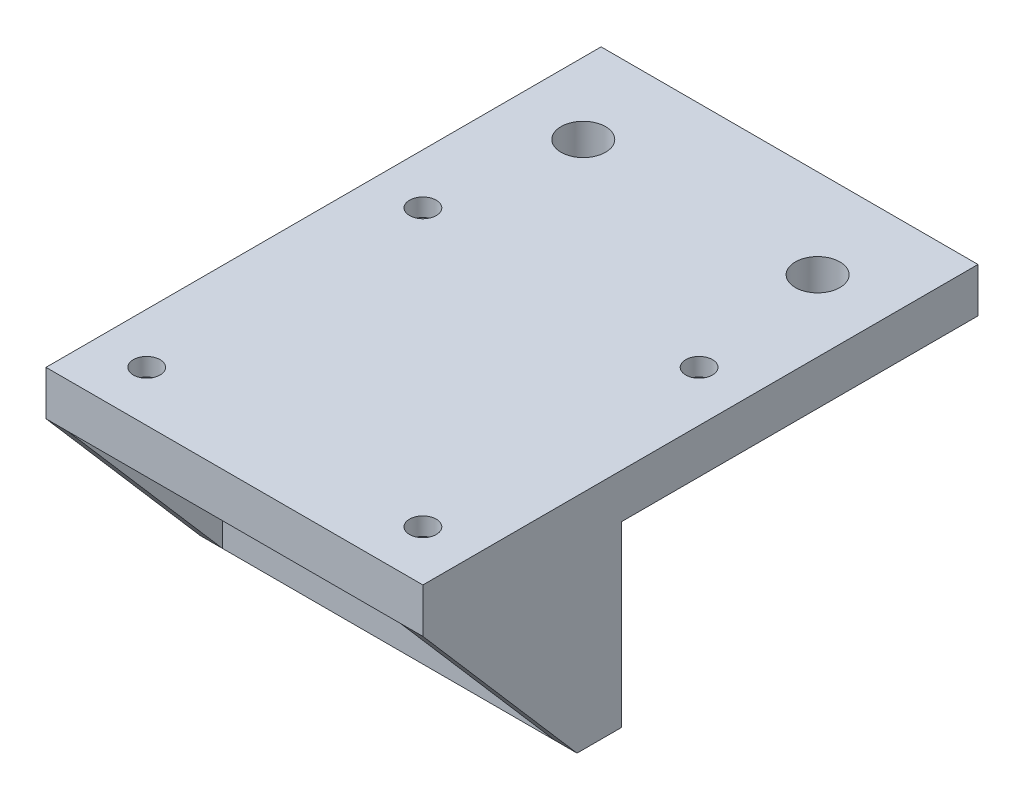
SolidWorks part; units mm, degrees
material "PET"
ref_plane "Front Plane" through (0, 0, 0) normal (0, 0, 1) x (1, 0, 0)
ref_plane "Top Plane" through (0, 0, 0) normal (0, 1, 0) x (1, 0, 0)
ref_plane "Right Plane" through (0, 0, 0) normal (1, 0, 0) x (0, 0, -1)
sketch "Sketch1" plane through (0, 0, 0) normal (0, 1, 0) x (1, 0, 0)
  line L0 (21.15, 21.15) -> (-21.15, -21.15) construction
  line L1 (-21.15, -21.15) -> (21.15, -21.15)
  line L2 (-21.15, -21.15) -> (-21.15, 21.15)
  line L4 (21.15, -21.15) -> (21.15, 21.15)
  line L5 (-15.5, 15.5) -> (15.5, -15.5) construction
  line L8 (-21.15, 21.15) -> (-21.15, 41.15)
  line L9 (-21.15, 41.15) -> (21.15, 41.15)
  line L10 (21.15, 21.15) -> (21.15, 41.15)
  circle A0 centre (-15.5, 15.5) radius 1.5
  circle A1 centre (15.5, 15.5) radius 1.5
  circle A2 centre (-15.5, -15.5) radius 1.5
  circle A3 centre (15.5, -15.5) radius 1.5
  point P4 (0, 0)
  point P15 (0, 0)
  point P17 (0, 0)
  dimension "D3" = 3
  dimension "D4" = 3
  dimension "D5" = 3
  dimension "D7" = 3
  dimension "D1" = 20
  dimension "D2" = 42.3
  dimension "D6" = 31
  dimension "D8" = 31
extrude "Boss-Extrude1" add sketch "Sketch1" along normal blind 5
sketch "Sketch2" plane through (0, 0, 0) normal (0, -1, 0) x (1, 0, 0)
  circle A0 centre (-15.5, 15.5) radius 2.75
  circle A1 centre (-15.5, -15.5) radius 2.75
  circle A2 centre (15.5, 15.5) radius 2.75
  circle A3 centre (15.5, -15.5) radius 2.75
  dimension "D1" = 5.5
  dimension "D2" = 5.5
  dimension "D3" = 5.5
  dimension "D4" = 5.5
extrude "Cut-Extrude1" cut sketch "Sketch2" against normal blind 3
sketch "Sketch3" plane through (0, 0, 0) normal (0, -1, 0) x (1, 0, 0)
  line L0 (21.15, 21.15) -> (21.15, -41.15) construction
  line L1 (-21.15, -21.15) -> (21.15, -21.15)
  line L2 (-21.15, -21.15) -> (-21.15, -1.15)
  line L3 (-21.15, -1.15) -> (21.15, -1.15)
  line L4 (21.15, -21.15) -> (21.15, -1.15)
  line L5 (21.15, -41.15) -> (-21.15, -41.15) construction
  line L6 (21.15, -1.15) -> (-21.15, -1.15)
  line L7 (21.15, -1.15) -> (21.15, 3.85)
  line L8 (21.15, 3.85) -> (-21.15, 3.85)
  line L9 (-21.15, -1.15) -> (-21.15, 3.85)
  line L10 (-21.15, -41.15) -> (-21.15, 21.15) construction
  line M8 (-21.15, 21.15) -> (-21.15, -41.15)
  line M10 (21.15, -41.15) -> (21.15, 21.15)
  dimension "D1" = 5
  dimension "D2" = 20
  dimension "D3" = 20
extrude "Boss-Extrude2" add sketch "Sketch3" along normal blind 20 contours L8 L3 M10 M8 region at (0, 0, 1.35)
sketch "Sketch7" plane through (0, 1.15, 3.85) normal (0, 0, -1) x (1, 0, 0)
  line L1 (-21.15, 21.15) -> (21.15, 21.15) construction
  line L2 (-21.15, 21.15) -> (-21.15, 1.15) construction
  line L3 (-21.15, 1.15) -> (21.15, 1.15) construction
  line L4 (21.15, 21.15) -> (21.15, 1.15) construction
  line L5 (-21.15, 11.15) -> (21.15, 11.15) construction
  line L6 (21.15, 21.15) -> (-21.15, 21.15) construction
  line L7 (-21.15, 21.15) -> (-21.15, 1.15) construction
  line L8 (21.15, 21.15) -> (21.15, 1.15) construction
  circle A0 centre (-13.15, 11.15) radius 2.5
  circle A1 centre (13.15, 11.15) radius 2.5
  dimension "D2" = 5
  dimension "D3" = 5
  dimension "D1" = 20
  dimension "D4" = 8
  dimension "D5" = 8
extrude "Cut-Extrude4" cut sketch "Sketch7" along normal through all
sketch "Sketch8" plane through (0, 5, 0) normal (0, 1, 0) x (1, 0, 0)
  line L0 (21.15, 41.15) -> (-21.15, 41.15) construction
  line L1 (-21.15, 41.15) -> (-21.15, -21.15) construction
  line L2 (21.15, -21.15) -> (21.15, 41.15) construction
  circle A0 centre (-13.15, 31.15) radius 2.5
  circle A1 centre (13.15, 31.15) radius 2.5
  point P10 (0, 0)
  dimension "D1" = 5
  dimension "D2" = 5
  dimension "D3" = 10
  dimension "D4" = 8
  dimension "D5" = 8
extrude "Cut-Extrude5" cut sketch "Sketch8" against normal through all
sketch "Sketch9" plane through (-21.15, 0, 0) normal (-1, 0, 0) x (0, 0, 1)
  line L0 (3.85, -20) -> (21.15, 0)
rib "Rib1" sketch "Sketch9" sketch "Sketch9" thickness 2.5 extrusion direction parallel to sketch draft on no parameters "D1"=2.5
ref_plane "Plane1" through (0, 0, 0) normal (-1, 0, 0) x (0, 0, 1)
mirror "Mirror1" about plane through (0, 0, 0) normal (-1, 0, 0) of "Rib1"
